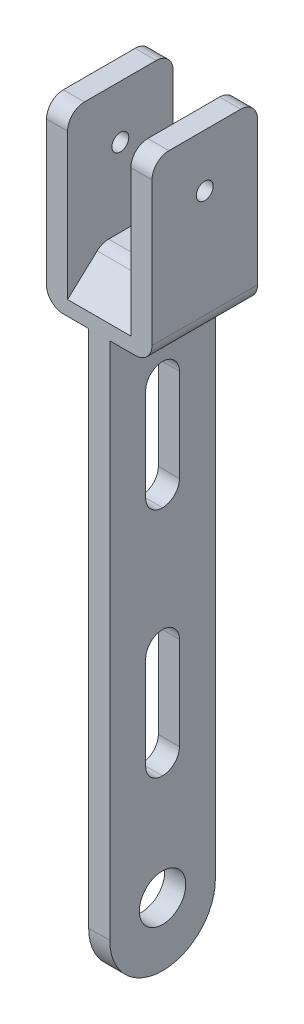
SolidWorks part; units mm, degrees
ref_plane "Ön Düzlem" through (0, 0, 0) normal (0, 0, 1) x (1, 0, 0)
ref_plane "Üst Düzlem" through (0, 0, 0) normal (0, 1, 0) x (1, 0, 0)
ref_plane "Sağ Düzlem" through (0, 0, 0) normal (1, 0, 0) x (0, 0, -1)
sketch "Çizim1" plane through (0, 0, 0) normal (0, 0, 1) x (1, 0, 0)
  line L0 (-2.5, 48) -> (-12.5, 48)
  line L1 (2.5, -87.5) -> (-2.5, -87.5)
  line L2 (2.5, -87.5) -> (2.5, 48)
  line L4 (-2.5, -87.5) -> (-2.5, 48)
  line L7 (-12.5, 48) -> (-12.5, 90)
  line L8 (-12.5, 90) -> (-7.5, 90)
  line L9 (-7.5, 90) -> (-7.5, 59)
  line L10 (-7.5, 59) -> (7.5, 59)
  line L11 (7.5, 59) -> (7.5, 90)
  line L12 (7.5, 90) -> (12.5, 90)
  line L13 (12.5, 90) -> (12.5, 48)
  line L14 (12.5, 48) -> (2.5, 48)
  point P0 (0, 0)
  dimension "D1" = 48
  dimension "D2" = 2.5
  dimension "D3" = 10
  dimension "D4" = 42
  dimension "D5" = 5
  dimension "D6" = 31
  dimension "D7" = 15
  dimension "D8" = 42
  dimension "D9" = 5
  dimension "D10" = 48
  dimension "D11" = 87.5
  dimension "D12" = 2.5
extrude "Yükseklik-Ekstrüzyon1" add sketch "Çizim1" along normal blind 25
sketch "Çizim2" plane through (-12.5, 0, 0) normal (-1, 0, 0) x (0, 0, 1)
  line L0 (0, 90) -> (0, 48) construction
  line L2 (25, 90) -> (0, 90) construction
  circle A0 centre (12.5, 77.5) radius 2
  dimension "D3" = 4
  dimension "D1" = 12.5
  dimension "D2" = 12.5
extrude "Kes-Ekstrüzyon1" cut sketch "Çizim2" against normal blind 25
sketch "Çizim3" plane through (-2.5, 0, 0) normal (-1, 0, 0) x (0, 0, 1)
  line L0 (25, 48) -> (25, -87.5) construction
  line L1 (8.5, 37.5) -> (16.5, 37.5)
  line L2 (8.5, 37.5) -> (8.5, 7.5)
  line L3 (8.5, 7.5) -> (16.5, 7.5)
  line L4 (16.5, 37.5) -> (16.5, 7.5)
  line L5 (8.5, -17.5) -> (16.5, -17.5)
  line L6 (8.5, -17.5) -> (8.5, -47.5)
  line L7 (8.5, -47.5) -> (16.5, -47.5)
  line L8 (16.5, -17.5) -> (16.5, -47.5)
  line L9 (25, -87.5) -> (0, -87.5) construction
  line L10 (0, 48) -> (0, -87.5) construction
  circle A0 centre (12.5, -72.5) radius 5.5
  dimension "D1" = 11
  dimension "D2" = 12.5
  dimension "D3" = 15
  dimension "D4" = 8.5
  dimension "D5" = 8.5
  dimension "D6" = 25
  dimension "D7" = 40
  dimension "D8" = 30
  dimension "D9" = 30
  dimension "D10" = 8.5
  dimension "D11" = 8.5
extrude "Kes-Ekstrüzyon2" cut sketch "Çizim3" against normal blind 10
ref_plane "Plane1" through (0, 0, 0) normal (1, 0, 0) x (0, 0, -1)
sketch "Sketch2" plane through (0, 0, 0) normal (1, 0, 0) x (0, 0, -1)
  line L0 (-12.5, 0) -> (-12.5, 63) construction
  line L4 (0, 0) -> (-27.6764, 0) construction
  line L6 (-12.5, 63) -> (-25.5, 51)
  line L8 (-12.5, 63) -> (0.5, 51)
  line L9 (0.5, 51) -> (0.5, 65)
  line L10 (-25.5, 51) -> (-25.5, 65)
  line L11 (0.5, 65) -> (-25.5, 65)
  dimension "D1" = 12.5
  dimension "D2" = 63
  dimension "D3" = 13
  dimension "D4" = 13
  dimension "D5" = 12
  dimension "D6" = 12
  dimension "D7" = 14
  dimension "D8" = 14
extrude "Cut-Extrude8" cut sketch "Sketch2" against normal mid plane 15
fillet "Radyus1" radius 4 16 edges at (-10, 90, 25) (10, 90, 25) (10, 90, 0) (-10, 90, 0) (0, 7.5, 16.5) (0, 37.5, 16.5) (0, 7.5, 8.5) (0, 37.5, 8.5) (0, -47.5, 16.5) (0, -47.5, 8.5) (0, -17.5, 16.5) (0, -17.5, 8.5) (0, 59, 16.8333) (0, 59, 8.1667) (12.5, 48, 12.5) (-12.5, 48, 12.5)
fillet "Fillet1" radius 12.5 2 edges at (0, -87.5, 0) (0, -87.5, 25)
